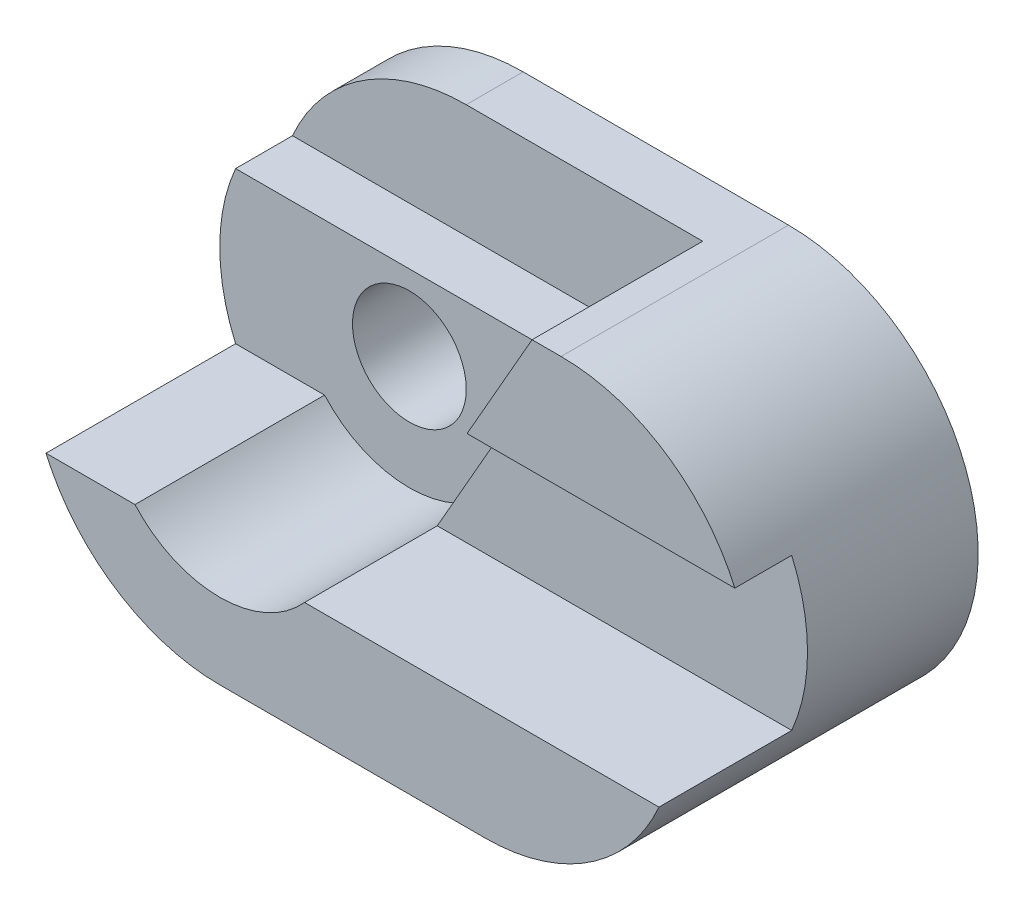
SolidWorks part; units mm, degrees
ref_plane "Front Plane" through (0, 0, 0) normal (0, 0, 1) x (1, 0, 0)
ref_plane "Top Plane" through (0, 0, 0) normal (0, 1, 0) x (1, 0, 0)
ref_plane "Right Plane" through (0, 0, 0) normal (1, 0, 0) x (0, 0, -1)
sketch "Sketch2" plane through (0, 0, 0) normal (0, 0, 1) x (1, 0, 0)
  line L0 (-3.5, 0) -> (3.5, 0) construction
  line L1 (-3.5, 5) -> (3.5, 5)
  line L2 (-3.5, -5) -> (3.5, -5)
  arc A0 (-3.5, 5) -> (-3.5, -5) centre (-3.5, 0) ccw
  arc A1 (3.5, -5) -> (3.5, 5) centre (3.5, 0) ccw
  circle A2 centre (-3.5, 0) radius 1.5
  point P3 (0, 0)
  dimension "D3" = 5
  dimension "D4" = 3
  dimension "D1" = 0
  dimension "D2" = 7
extrude "Boss-Extrude1" add sketch "Sketch2" along normal blind 8
sketch "Sketch3" plane through (0, 0, 0) normal (1, 0, 0) x (0, 0, -1)
  line L0 (-8, -2) -> (-4.5, -2)
  line L1 (-8, 5) -> (-8, -5) construction
  line L2 (-4.5, -2) -> (-4.5, 2)
  line L3 (-4.5, 2) -> (-6, 2)
  line L4 (-6, 2) -> (-6, 5)
  line L5 (-8, 5) -> (0, 5) construction
  line L6 (-6, 5) -> (-8, 5)
  line L7 (-8, 5) -> (-8, -2)
  line L8 (-8, -5) -> (0, -5) construction
  dimension "D1" = 3
  dimension "D2" = 3.5
  dimension "D3" = 4
  dimension "D4" = 2
extrude "Cut-Extrude1" cut sketch "Sketch3" against normal blind 18 and the other way blind 18
sketch "Sketch4" plane through (0, 0, 8) normal (0, 0, 1) x (1, 0, 0)
  line L0 (8.0826, -2) -> (-8.0826, -2) construction
  line L1 (-1.2639, -2) -> (2.7361, 5)
  line L2 (3.5, 5) -> (-3.5, 5) construction
  line L3 (2.7361, 5) -> (-10.7872, 5)
  line L4 (-10.7872, 5) -> (-10.7872, -2)
  line L5 (-10.7872, -2) -> (-5.7361, -2)
  arc A0 (-5.7361, -2) -> (-1.2639, -2) centre (-3.5, 0) ccw
  dimension "D1" = 3
  dimension "D2" = 4
extrude "Cut-Extrude2" cut sketch "Sketch4" against normal blind 5
sketch "Sketch5" plane through (0, 0, 3) normal (0, 0, 1) x (1, 0, 0)
  line L0 (1.0218, 2) -> (2.7361, 5)
  line L1 (2.7361, 5) -> (-9.1994, 5)
  line L2 (-9.1994, 5) -> (-9.1994, 2)
  line L3 (-9.1994, 2) -> (1.0218, 2)
extrude "Cut-Extrude3" cut sketch "Sketch5" against normal blind 1.5
